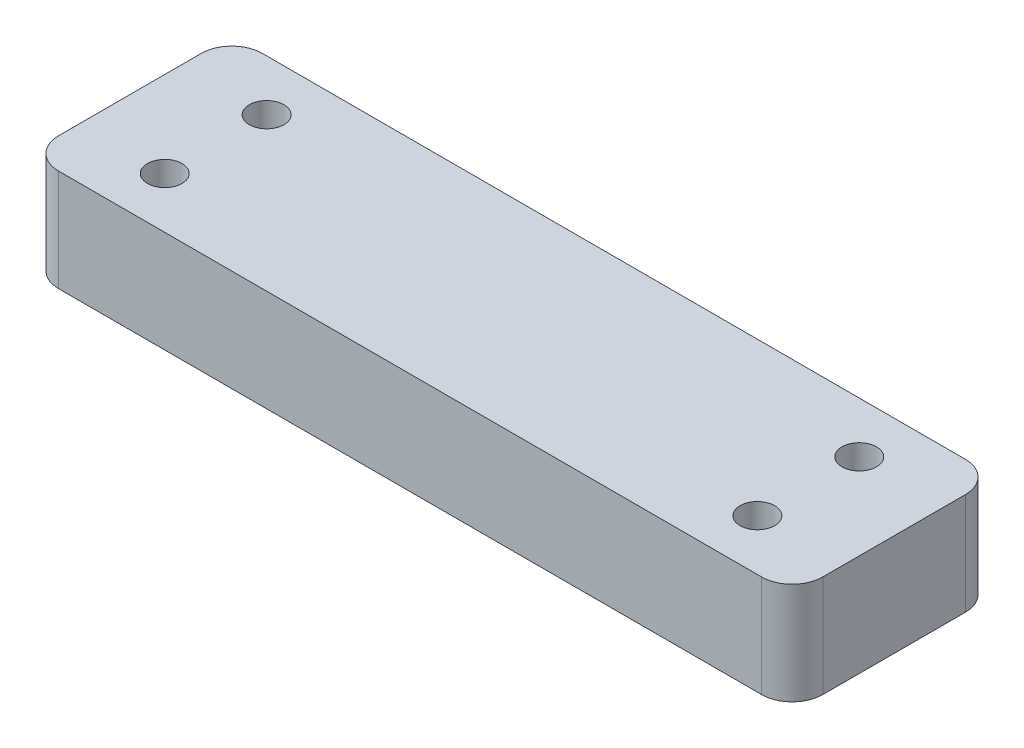
SolidWorks part; units mm, degrees
ref_plane "Front Plane" through (0, 0, 0) normal (0, 0, 1) x (1, 0, 0)
ref_plane "Top Plane" through (0, 0, 0) normal (0, 1, 0) x (1, 0, 0)
ref_plane "Right Plane" through (0, 0, 0) normal (1, 0, 0) x (0, 0, -1)
sketch "Sketch1" plane through (0, 0, 0) normal (0, 1, 0) x (1, 0, 0)
  line L1 (0, 0) -> (75, 0)
  line L2 (0, 0) -> (0, 20)
  line L3 (0, 20) -> (75, 20)
  line L4 (75, 0) -> (75, 20)
  dimension "D1" = 75
  dimension "D2" = 20
extrude "Boss-Extrude1" add sketch "Sketch1" along normal blind 10
fillet "Fillet1" radius 3 4 edges at (0, 5, -20) (0, 5, 0) (75, 5, -20) (75, 5, 0)
hole_wizard "M3 Clearance Hole1" positions "Sketch2" profile "Sketch3" hole size "M3" standard "ANSI Metric" end condition through all
sketch "Sketch2" plane through (50.0353, 10, -35.4163) normal (0, 1, 0) x (1, 0, 0)
  point P0 (16.5457, -20.4163)
  point P1 (16.5457, -30.4163)
  point P4 (-41.6163, -30.4163)
  point P5 (-41.6163, -20.4163)
sketch "Sketch3" plane through (66.581, 10, -15) normal (1, 0, 0) x (0, 0, 1)
  line L0 (0, 0) -> (0, 10)
  line L1 (0, 10) -> (1.7, 10)
  line L2 (1.7, 10) -> (1.7, 0)
  line L3 (1.7, 0) -> (0, 0)
  line L4 (0, -6.35) -> (0, 107.95) construction
  dimension "Thru Hole Dia." = 3.4
  dimension "Thru Hole Depth" = 10
